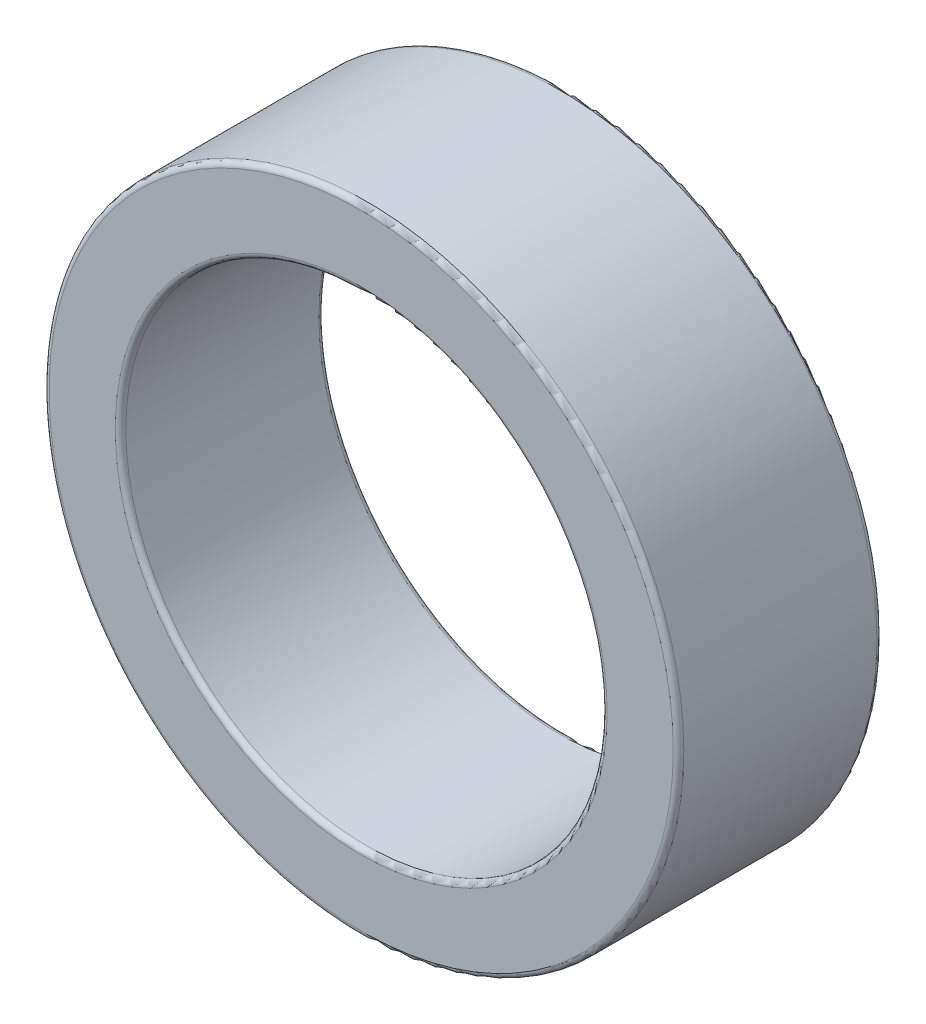
SolidWorks part; units mm, degrees
material "6061 Alloy"
ref_plane "前基準面" through (0, 0, 0) normal (0, 0, 1) x (1, 0, 0)
ref_plane "上基準面" through (0, 0, 0) normal (0, 1, 0) x (1, 0, 0)
ref_plane "右基準面" through (0, 0, 0) normal (1, 0, 0) x (0, 0, -1)
sketch "Sketch1" plane through (0, 0, 0) normal (0, 0, 1) x (1, 0, 0)
  circle A0 centre (0, 0) radius 4.55
  circle A1 centre (0, 0) radius 6
  dimension "D1" = 9.1
  dimension "D2" = 12
extrude "Boss-Extrude1" add sketch "Sketch1" along normal blind 3.85
fillet "Fillet1" radius 0.1 4 edges at (4.55, 0, 0) (6, 0, 0) (4.55, 0, 3.85) (6, 0, 3.85)
